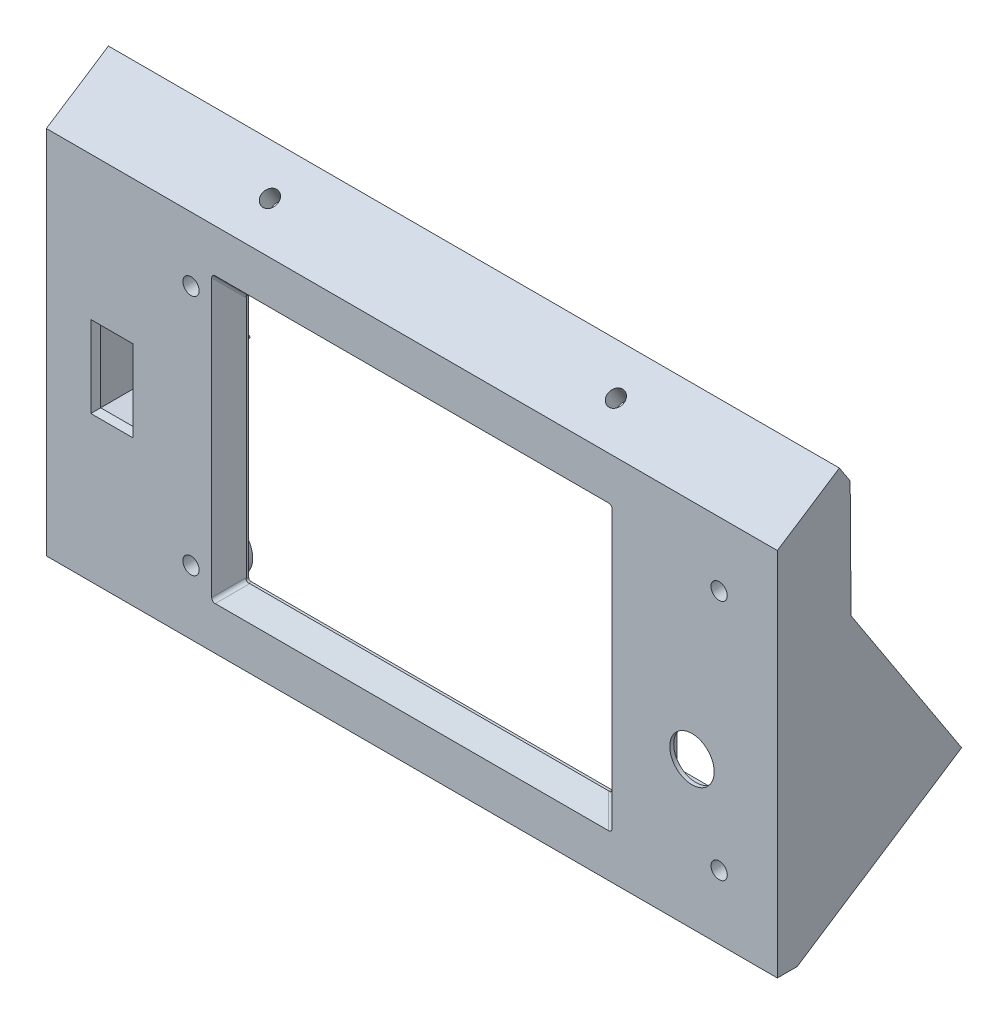
SolidWorks part; units mm, degrees
ref_plane "前视基准面" through (0, 0, 0) normal (0, 0, 1) x (1, 0, 0)
ref_plane "上视基准面" through (0, 0, 0) normal (0, 1, 0) x (1, 0, 0)
ref_plane "右视基准面" through (0, 0, 0) normal (1, 0, 0) x (0, 0, -1)
sketch "草图1" plane through (0, 0, 0) normal (0, 0, 1) x (1, 0, 0)
  line L1 (0, 0) -> (148.1, 0)
  line L2 (0, 0) -> (0, 75)
  line L3 (0, 75) -> (148.1, 75)
  line L4 (148.1, 0) -> (148.1, 75)
  line L5 (37, 62.75) -> (111.1, 62.75)
  line L6 (37, 62.75) -> (37, 12.25)
  line L7 (37, 12.25) -> (111.1, 12.25)
  line L8 (111.1, 62.75) -> (111.1, 12.25)
  line L9 (10, 45) -> (16.5, 45)
  line L10 (10, 45) -> (10, 30.5)
  line L11 (10, 30.5) -> (16.5, 30.5)
  line L12 (16.5, 45) -> (16.5, 30.5)
  circle A0 centre (29.3, 62) radius 1.65
  circle A1 centre (136.3, 62) radius 1.65
  circle A2 centre (136.3, 13) radius 1.65
  circle A3 centre (29.3, 13) radius 1.65
  circle A4 centre (130.8, 29.75) radius 4.5
  point P17 (111.1, 37.5)
  point P18 (148.1, 37.5)
  dimension "D11" = 9
  dimension "D12" = 3.3
  dimension "D18" = 37
  dimension "D2" = 75
  dimension "D3" = 74.1
  dimension "D4" = 50.5
  dimension "D5" = 107
  dimension "D6" = 49
  dimension "D7" = 19.7
  dimension "D8" = 13
  dimension "D9" = 25.2
  dimension "D10" = 17.5
  dimension "D13" = 37
  dimension "D14" = 30
  dimension "D15" = 10
  dimension "D16" = 14.5
  dimension "D17" = 6.5
extrude "凸台-拉伸1" add sketch "草图1" along normal blind 4
sketch "草图2" plane through (0, 0, 0) normal (0, 0, -1) x (-1, 0, 0)
  line L1 (-137.8, 36.75) -> (-123.8, 36.75)
  line L2 (-137.8, 36.75) -> (-137.8, 22.75)
  line L3 (-137.8, 22.75) -> (-123.8, 22.75)
  line L4 (-123.8, 36.75) -> (-123.8, 22.75)
  circle A1 centre (-130.8, 29.75) radius 4.5 construction
  dimension "D1" = 7
  dimension "D2" = 7
  dimension "D3" = 14
  dimension "D4" = 14
extrude "切除-拉伸1" cut sketch "草图2" against normal blind 3.2
chamfer "倒角1" distance 3.5 angle 45 4 edges at (74.05, 12.25, 4) (37, 37.5, 4) (74.05, 62.75, 4) (111.1, 37.5, 4)
fillet "圆角1" radius 0.5 4 edges at (37, 12.25, 0.25) (111.1, 12.25, 0.25) (111.1, 62.75, 0.25) (37, 62.75, 0.25)
fillet "圆角2" radius 1 4 edges at (35.3232, 10.5732, 2.1768) (112.7768, 10.5732, 2.1768) (112.7768, 64.4268, 2.1768) (35.3232, 64.4268, 2.1768)
sketch "草图4" plane through (0, 0, 0) normal (0, 0, -1) x (-1, 0, 0)
  circle A0 centre (-29.3, 62) radius 5
  circle A1 centre (-29.3, 13) radius 5
  circle A2 centre (-136.3, 62) radius 5
  circle A3 centre (-136.3, 13) radius 5
  circle A4 centre (-136.3, 62) radius 1.65 construction
  circle A5 centre (-136.3, 13) radius 1.65 construction
  circle A6 centre (-29.3, 13) radius 1.65 construction
  circle A7 centre (-29.3, 62) radius 1.65 construction
  circle A8 centre (-136.3, 62) radius 1.65
  circle A9 centre (-136.3, 13) radius 1.65
  circle A10 centre (-29.3, 13) radius 1.65
  circle A11 centre (-29.3, 62) radius 1.65
  dimension "D1" = 10
extrude "凸台-拉伸2" add sketch "草图4" along normal blind 3.5
sketch "草图5" plane through (0, 0, 0) normal (0, 0, -1) x (-1, 0, 0)
  line L0 (-10, 30.5) -> (-16.5, 30.5) construction
  line L1 (-21.5, 50) -> (-5, 50)
  line L2 (-21.5, 50) -> (-21.5, 25.5)
  line L3 (-21.5, 25.5) -> (-5, 25.5)
  line L4 (-5, 50) -> (-5, 25.5)
  line L5 (-10, 45) -> (-10, 30.5) construction
  line L6 (-16.5, 30.5) -> (-16.5, 45) construction
  line L7 (-16.5, 45) -> (-10, 45) construction
  line L8 (-10, 30.5) -> (-16.5, 30.5)
  line L9 (-10, 45) -> (-10, 30.5)
  line L10 (-16.5, 30.5) -> (-16.5, 45)
  line L11 (-16.5, 45) -> (-10, 45)
  dimension "D1" = 5
  dimension "D2" = 5
  dimension "D3" = 5
  dimension "D4" = 5
extrude "凸台-拉伸3" add sketch "草图5" along normal blind 9
chamfer "倒角2" distance 1 angle 45 4 edges at (13.25, 30.5, 4) (16.5, 37.75, 4) (13.25, 45, 4) (10, 37.75, 4)
sketch "草图6" plane through (148.1, 0, 0) normal (1, 0, 0) x (0, 0, -1)
  line L0 (-4, 75) -> (8.5629, 83.196)
  line L1 (8.5629, 83.196) -> (10.7485, 79.8459)
  line L2 (10.7485, 79.8459) -> (0, 72.8336)
  line L3 (0, 0) -> (0, 75) construction
  line L4 (0, 72.8336) -> (33.3303, 21.7446)
  line L5 (33.3303, 21.7446) -> (0, 0)
  line L6 (0, 0) -> (-4, 0)
  line L7 (-4, 0) -> (-4, 75)
  dimension "D1" = 15
  dimension "D2" = 4
  dimension "D3" = 65
extrude "凸台-拉伸4" add sketch "草图6" against normal blind 4
sketch "草图7" plane through (0, 0, 0) normal (-1, 0, 0) x (0, 0, 1)
  line L7 (0, 72.8336) -> (-33.3303, 21.7446)
  line L8 (-10.7485, 79.8459) -> (0, 72.8336)
  line L9 (-8.5629, 83.196) -> (-10.7485, 79.8459)
  line L10 (4, 75) -> (-8.5629, 83.196)
  line L11 (4, 0) -> (4, 75)
  line L12 (0, 0) -> (4, 0)
  line L13 (-33.3303, 21.7446) -> (0, 0)
  line L14 (0, 72.8336) -> (-33.3303, 21.7446)
  line L15 (-10.7485, 79.8459) -> (0, 72.8336)
  line L16 (-8.5629, 83.196) -> (-10.7485, 79.8459)
  line L17 (4, 75) -> (-8.5629, 83.196)
  line L18 (4, 0) -> (4, 75)
  line L19 (0, 0) -> (4, 0)
  line L20 (-33.3303, 21.7446) -> (0, 0)
  dimension "D1" = 0
extrude "凸台-拉伸5" add sketch "草图7" against normal blind 4
sketch "草图8" plane through (0, 54.4392, 35.5159) normal (0, 0.8375, 0.5464) x (1, 0, 0)
  line L1 (144.1, 37.6298) -> (4, 37.6298)
  line L2 (144.1, 37.6298) -> (144.1, 52.6298)
  line L3 (144.1, 52.6298) -> (4, 52.6298)
  line L4 (4, 37.6298) -> (4, 52.6298)
  circle A0 centre (39, 45.1298) radius 1.65
  circle A1 centre (109.1, 45.1298) radius 1.65
  dimension "D4" = 3.3
  dimension "D1" = 35
  dimension "D2" = 35
  dimension "D3" = 7.5
extrude "凸台-拉伸6" add sketch "草图8" against normal blind 4
sketch "草图9" plane through (148.1, 0, 0) normal (1, 0, 0) x (0, 0, -1)
  line L0 (10.7485, 79.8459) -> (0, 72.8336)
  line L1 (0, 72.8336) -> (10.928, 56.0831)
  line L2 (33.3303, 21.7446) -> (0, 72.8336) construction
  line L3 (10.928, 56.0831) -> (10.7485, 79.8459)
  dimension "D1" = 20
extrude "凸台-拉伸7" add sketch "草图9" against normal blind 4
sketch "草图10" plane through (0, 0, 0) normal (-1, 0, 0) x (0, 0, 1)
  line L0 (-10.7485, 79.8459) -> (0, 72.8336)
  line L1 (0, 72.8336) -> (-10.928, 56.0831)
  line L3 (-10.928, 56.0831) -> (-10.7485, 79.8459)
  line L4 (0, 72.8336) -> (-33.3303, 21.7446) construction
  point P4 (0, 0)
  dimension "D1" = 20
extrude "凸台-拉伸8" add sketch "草图10" against normal blind 4
